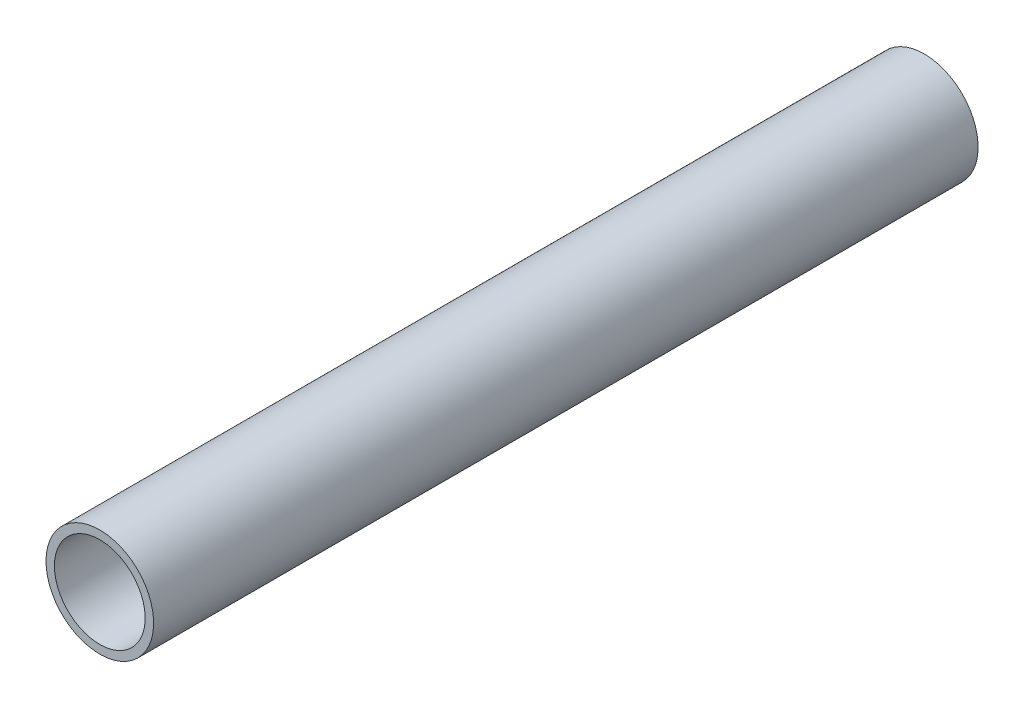
SolidWorks part; units mm, degrees
ref_plane "Front Plane" through (0, 0, 0) normal (0, 0, 1) x (1, 0, 0)
ref_plane "Top Plane" through (0, 0, 0) normal (0, 1, 0) x (1, 0, 0)
ref_plane "Right Plane" through (0, 0, 0) normal (1, 0, 0) x (0, 0, -1)
sketch "Sketch1" plane through (0, 0, 0) normal (0, 0, 1) x (1, 0, 0)
  line L0 (-7.9375, 0) -> (7.9375, 0) construction
  line L1 (0, -7.9375) -> (0, 7.9375) construction
  circle A0 centre (0, 0) radius 7.9375
  circle A1 centre (0, 0) radius 6.6929
  point P4 (0, 0)
  point P9 (0, 0)
  point P10 (6.6929, 0)
  dimension "ID" = 13.3858
  dimension "OD" = 15.875
  dimension "Wall Thickness" = 1.2446
sketch "Sketch2" plane through (0, 0, 0) normal (1, 0, 0) x (0, 0, -1)
  line L0 (60.8152, 7.9375) -> (-60.8152, 7.9375) construction
  line L1 (0, 7.9375) -> (0, -7.9375) construction
  point P3 (-42.559, 7.9375)
  point P4 (0, 7.9375)
  point P5 (42.559, 7.9375)
  dimension "Length" = 121.6305
  dimension "D1" = 18.2563
  dimension "D2" = 18.2562
sketch "Sketch3" plane through (0, 0, 0) normal (0, 0, 1) x (1, 0, 0)
  line L0 (0, -7.9375) -> (0, 7.9375) construction
  circle A0 centre (0, 0) radius 7.9375
  circle A1 centre (0, 0) radius 6.6929
  circle A2 centre (0, 0) radius 6.6929 construction
extrude "Boss-Extrude1" add sketch "Sketch3" along normal mid plane 121.6305
equation "\"D1@Boss-Extrude1\" = \"Length@Sketch2\""
equation "\"D1@Sketch2\"=\"OD@Sketch1\"*1.15"
equation "\"D2@Sketch2\"=\"D1@Sketch2\""
